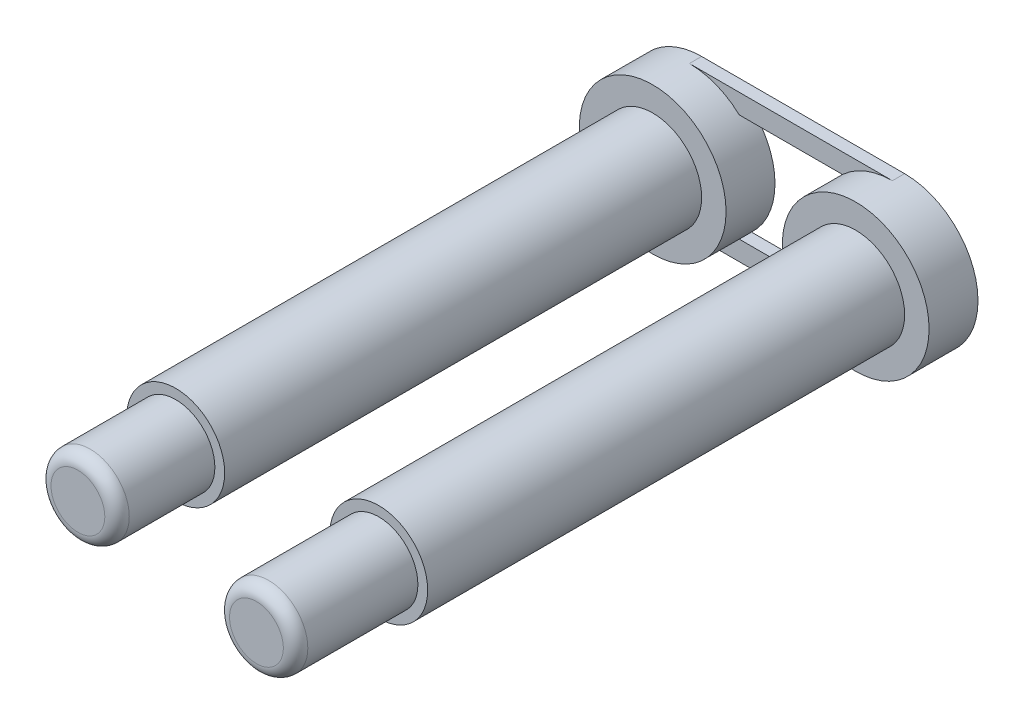
SolidWorks part; units mm, degrees
ref_plane "前视基准面" through (0, 0, 0) normal (0, 0, 1) x (1, 0, 0)
ref_plane "上视基准面" through (0, 0, 0) normal (0, 1, 0) x (1, 0, 0)
ref_plane "右视基准面" through (0, 0, 0) normal (1, 0, 0) x (0, 0, -1)
sketch "Model" plane through (0, 0, 0) normal (0, 0, 1) x (1, 0, 0)
  line L0 (0, 2.26) -> (0, 39.4058)
  line L1 (2.4326, 41.5) -> (50.1564, 41.5)
  line L2 (52.5, 39.422) -> (52.5, 2.28)
  line L3 (50.22, 0) -> (2.26, 0)
  line L4 (0.57, 8.85) -> (-6.93, 8.85)
  line L5 (-6.93, 8.85) -> (-6.93, 24.85)
  line L6 (-6.93, 24.85) -> (0.57, 24.85)
  line L7 (16.57, 8.85) -> (17.57, 8.85)
  line L8 (17.57, 8.85) -> (17.57, 10.85)
  line L9 (17.57, 22.85) -> (17.57, 24.85)
  line L10 (17.57, 24.85) -> (16.57, 24.85)
  line L11 (24.196, 8.775) -> (23.307, 8.775)
  line L12 (22.926, 9.156) -> (22.926, 9.664)
  line L13 (23.307, 10.045) -> (24.196, 10.045)
  line L14 (24.704, 10.045) -> (25.593, 10.045)
  line L15 (25.974, 9.664) -> (25.974, 9.156)
  line L16 (25.593, 8.775) -> (24.704, 8.775)
  line L17 (34.756, 17.315) -> (33.867, 17.315)
  line L18 (33.486, 17.696) -> (33.486, 18.204)
  line L19 (33.867, 18.585) -> (34.756, 18.585)
  line L20 (35.264, 18.585) -> (36.153, 18.585)
  line L21 (36.534, 18.204) -> (36.534, 17.696)
  line L22 (36.153, 17.315) -> (35.264, 17.315)
  line L23 (16.835, 4.806) -> (16.835, 3.917)
  line L24 (16.454, 3.536) -> (15.946, 3.536)
  line L25 (15.565, 3.917) -> (15.565, 4.806)
  line L26 (15.565, 5.314) -> (15.565, 6.203)
  line L27 (15.946, 6.584) -> (16.454, 6.584)
  line L28 (16.835, 6.203) -> (16.835, 5.314)
  line L29 (26.454, 3.425) -> (27.343, 3.425)
  line L30 (27.724, 3.044) -> (27.724, 2.536)
  line L31 (27.343, 2.155) -> (26.454, 2.155)
  line L32 (25.946, 2.155) -> (25.057, 2.155)
  line L33 (24.676, 2.536) -> (24.676, 3.044)
  line L34 (25.057, 3.425) -> (25.946, 3.425)
  line L35 (18.255, 4.756) -> (18.255, 3.867)
  line L36 (17.874, 3.486) -> (17.366, 3.486)
  line L37 (16.985, 3.867) -> (16.985, 4.756)
  line L38 (16.985, 5.264) -> (16.985, 6.153)
  line L39 (17.366, 6.534) -> (17.874, 6.534)
  line L40 (18.255, 6.153) -> (18.255, 5.264)
  line L41 (12.8, 35.75) -> (12.8, 38.8)
  line L42 (12.8, 38.8) -> (14.05, 39.95)
  line L43 (14.05, 39.95) -> (16.45, 39.95)
  line L44 (16.45, 39.95) -> (17.6, 38.9)
  line L45 (17.6, 38.9) -> (17.6, 35.7)
  line L46 (17.6, 35.7) -> (16.45, 34.65)
  line L47 (16.45, 34.65) -> (14, 34.65)
  line L48 (14, 34.65) -> (12.8, 35.75)
  line L49 (3.87, 5.53) -> (6.67, 5.53)
  line L50 (6.67, 5.53) -> (6.67, 4.13)
  line L51 (6.67, 4.13) -> (3.87, 4.13)
  line L52 (3.87, 4.13) -> (3.87, 5.53)
  line L53 (20.8, 6.56) -> (20.8, 9.36)
  line L54 (20.8, 9.36) -> (22.2, 9.36)
  line L55 (22.2, 9.36) -> (22.2, 6.56)
  line L56 (22.2, 6.56) -> (20.8, 6.56)
  line L57 (8.21, 6.97) -> (8.21, 4.17)
  line L58 (8.21, 4.17) -> (6.81, 4.17)
  line L59 (6.81, 4.17) -> (6.81, 6.97)
  line L60 (6.81, 6.97) -> (8.21, 6.97)
  line L61 (10.82, 29.94) -> (10.82, 27.14)
  line L62 (10.82, 27.14) -> (9.42, 27.14)
  line L63 (9.42, 27.14) -> (9.42, 29.94)
  line L64 (9.42, 29.94) -> (10.82, 29.94)
  line L65 (33.69, 12.87) -> (30.89, 12.87)
  line L66 (30.89, 12.87) -> (30.89, 14.27)
  line L67 (30.89, 14.27) -> (33.69, 14.27)
  line L68 (33.69, 14.27) -> (33.69, 12.87)
  line L69 (14.93, 29.94) -> (14.93, 27.14)
  line L70 (14.93, 27.14) -> (13.53, 27.14)
  line L71 (13.53, 27.14) -> (13.53, 29.94)
  line L72 (13.53, 29.94) -> (14.93, 29.94)
  line L73 (26.13, 4.53) -> (26.37, 4.53)
  line L74 (26.37, 4.53) -> (26.37, 7.36)
  line L75 (26.37, 7.36) -> (26.13, 7.36)
  line L76 (22.89, 4.53) -> (22.6, 4.53)
  line L77 (22.6, 4.53) -> (22.6, 7.37)
  line L78 (22.6, 7.37) -> (22.87, 7.37)
  line L79 (1.79, 29.79) -> (6.87, 29.79)
  line L80 (6.87, 29.79) -> (6.87, 27.25)
  line L81 (6.87, 27.25) -> (1.79, 27.25)
  line L82 (1.79, 27.25) -> (1.79, 29.79)
  line L83 (29.996, 38.955) -> (29.107, 38.955)
  line L84 (28.726, 39.336) -> (28.726, 39.844)
  line L85 (29.107, 40.225) -> (29.996, 40.225)
  line L86 (30.504, 40.225) -> (31.393, 40.225)
  line L87 (31.774, 39.844) -> (31.774, 39.336)
  line L88 (31.393, 38.955) -> (30.504, 38.955)
  line L89 (35.825, 11.706) -> (35.825, 10.817)
  line L90 (35.444, 10.436) -> (34.936, 10.436)
  line L91 (34.555, 10.817) -> (34.555, 11.706)
  line L92 (34.555, 12.214) -> (34.555, 13.103)
  line L93 (34.936, 13.484) -> (35.444, 13.484)
  line L94 (35.825, 13.103) -> (35.825, 12.214)
  line L95 (31.416, 6.905) -> (30.527, 6.905)
  line L96 (30.146, 7.286) -> (30.146, 7.794)
  line L97 (30.527, 8.175) -> (31.416, 8.175)
  line L98 (31.924, 8.175) -> (32.813, 8.175)
  line L99 (33.194, 7.794) -> (33.194, 7.286)
  line L100 (32.813, 6.905) -> (31.924, 6.905)
  line L101 (27.125, 13.384) -> (27.125, 14.273)
  line L102 (27.506, 14.654) -> (28.014, 14.654)
  line L103 (28.395, 14.273) -> (28.395, 13.384)
  line L104 (28.395, 12.876) -> (28.395, 11.987)
  line L105 (28.014, 11.606) -> (27.506, 11.606)
  line L106 (27.125, 11.987) -> (27.125, 12.876)
  line L107 (2.726, 5.765) -> (1.837, 5.765)
  line L108 (1.456, 6.146) -> (1.456, 6.654)
  line L109 (1.837, 7.035) -> (2.726, 7.035)
  line L110 (3.234, 7.035) -> (4.123, 7.035)
  line L111 (4.504, 6.654) -> (4.504, 6.146)
  line L112 (4.123, 5.765) -> (3.234, 5.765)
  line L113 (38.274, 36.345) -> (39.163, 36.345)
  line L114 (39.544, 35.964) -> (39.544, 35.456)
  line L115 (39.163, 35.075) -> (38.274, 35.075)
  line L116 (37.766, 35.075) -> (36.877, 35.075)
  line L117 (36.496, 35.456) -> (36.496, 35.964)
  line L118 (36.877, 36.345) -> (37.766, 36.345)
  line L119 (35.295, 38.504) -> (35.295, 39.393)
  line L120 (35.676, 39.774) -> (36.184, 39.774)
  line L121 (36.565, 39.393) -> (36.565, 38.504)
  line L122 (36.565, 37.996) -> (36.565, 37.107)
  line L123 (36.184, 36.726) -> (35.676, 36.726)
  line L124 (35.295, 37.107) -> (35.295, 37.996)
  line L125 (31.265, 4.376) -> (31.265, 3.487)
  line L126 (30.884, 3.106) -> (30.376, 3.106)
  line L127 (29.995, 3.487) -> (29.995, 4.376)
  line L128 (29.995, 4.884) -> (29.995, 5.773)
  line L129 (30.376, 6.154) -> (30.884, 6.154)
  line L130 (31.265, 5.773) -> (31.265, 4.884)
  line L131 (33.42, 4.7325) -> (33.42, 6.15)
  line L132 (33.42, 6.15) -> (31.5, 6.15)
  line L133 (31.5, 6.15) -> (31.5, 4.7325)
  line L134 (33.42, 2.8275) -> (33.42, 1.43)
  line L135 (33.42, 1.43) -> (31.5, 1.43)
  line L136 (31.5, 1.43) -> (31.5, 2.8275)
  line L137 (37.99, 12.2925) -> (37.99, 13.71)
  line L138 (37.99, 13.71) -> (36.07, 13.71)
  line L139 (36.07, 13.71) -> (36.07, 12.2925)
  line L140 (37.99, 10.3875) -> (37.99, 8.99)
  line L141 (37.99, 8.99) -> (36.07, 8.99)
  line L142 (36.07, 8.99) -> (36.07, 10.3875)
  line L143 (37.074, 38.3336) -> (37.074, 37.343)
  line L144 (37.582, 36.835) -> (38.6488, 36.835)
  line L145 (39.106, 37.3176) -> (39.106, 38.3336)
  line L146 (37.074, 39.1464) -> (37.074, 40.137)
  line L147 (37.582, 40.645) -> (38.6488, 40.645)
  line L148 (39.106, 40.1624) -> (39.106, 39.1464)
  line L149 (33.975, 16.983) -> (31.689, 16.983)
  line L150 (31.689, 16.983) -> (31.689, 14.697)
  line L151 (31.689, 14.697) -> (33.975, 14.697)
  line L152 (35.245, 16.983) -> (37.15, 16.983)
  line L153 (37.15, 16.983) -> (37.531, 16.602)
  line L154 (37.531, 16.602) -> (37.531, 15.078)
  line L155 (37.531, 15.078) -> (37.15, 14.697)
  line L156 (37.15, 14.697) -> (35.245, 14.697)
  line L157 (21.1, 35.75) -> (21.1, 38.8)
  line L158 (21.1, 38.8) -> (22.35, 39.95)
  line L159 (22.35, 39.95) -> (24.75, 39.95)
  line L160 (24.75, 39.95) -> (25.9, 38.9)
  line L161 (25.9, 38.9) -> (25.9, 35.7)
  line L162 (25.9, 35.7) -> (24.75, 34.65)
  line L163 (24.75, 34.65) -> (22.3, 34.65)
  line L164 (22.3, 34.65) -> (21.1, 35.75)
  line L165 (5.44, 35.75) -> (5.44, 38.8)
  line L166 (5.44, 38.8) -> (6.69, 39.95)
  line L167 (6.69, 39.95) -> (9.09, 39.95)
  line L168 (9.09, 39.95) -> (10.24, 38.9)
  line L169 (10.24, 38.9) -> (10.24, 35.7)
  line L170 (10.24, 35.7) -> (9.09, 34.65)
  line L171 (9.09, 34.65) -> (6.64, 34.65)
  line L172 (6.64, 34.65) -> (5.44, 35.75)
  line L173 (34.57, 3.22) -> (38.57, 3.22)
  line L174 (38.57, 3.22) -> (38.57, 8.72)
  line L175 (38.57, 8.72) -> (34.57, 8.72)
  line L176 (34.57, 8.72) -> (34.57, 3.22)
  line L177 (39.81, 30.07) -> (37.01, 30.07)
  line L178 (37.01, 30.07) -> (37.01, 31.47)
  line L179 (37.01, 31.47) -> (39.81, 31.47)
  line L180 (39.81, 31.47) -> (39.81, 30.07)
  line L181 (28.51, 40.17) -> (28.51, 37.37)
  line L182 (28.51, 37.37) -> (27.11, 37.37)
  line L183 (27.11, 37.37) -> (27.11, 40.17)
  line L184 (27.11, 40.17) -> (28.51, 40.17)
  line L185 (32.06, 40.25) -> (34.86, 40.25)
  line L186 (34.86, 40.25) -> (34.86, 38.85)
  line L187 (34.86, 38.85) -> (32.06, 38.85)
  line L188 (32.06, 38.85) -> (32.06, 40.25)
  line L189 (28.56, 11.71) -> (28.56, 14.51)
  line L190 (28.56, 14.51) -> (29.96, 14.51)
  line L191 (29.96, 14.51) -> (29.96, 11.71)
  line L192 (29.96, 11.71) -> (28.56, 11.71)
  line L193 (25.54, 13.29) -> (25.54, 16.09)
  line L194 (25.54, 16.09) -> (26.94, 16.09)
  line L195 (26.94, 16.09) -> (26.94, 13.29)
  line L196 (26.94, 13.29) -> (25.54, 13.29)
  line L197 (27.11, 11.4) -> (29.91, 11.4)
  line L198 (29.91, 11.4) -> (29.91, 10)
  line L199 (29.91, 10) -> (27.11, 10)
  line L200 (27.11, 10) -> (27.11, 11.4)
  line L201 (29.06, 8.4) -> (26.26, 8.4)
  line L202 (26.26, 8.4) -> (26.26, 9.8)
  line L203 (26.26, 9.8) -> (29.06, 9.8)
  line L204 (29.06, 9.8) -> (29.06, 8.4)
  line L205 (18.53, 32.56) -> (18.53, 29.76)
  line L206 (18.53, 29.76) -> (17.13, 29.76)
  line L207 (17.13, 29.76) -> (17.13, 32.56)
  line L208 (17.13, 32.56) -> (18.53, 32.56)
  line L209 (5.02, 31.95) -> (2.22, 31.95)
  line L210 (2.22, 31.95) -> (2.22, 33.35)
  line L211 (2.22, 33.35) -> (5.02, 33.35)
  line L212 (5.02, 33.35) -> (5.02, 31.95)
  line L213 (9.22, 29.96) -> (9.22, 27.16)
  line L214 (9.22, 27.16) -> (7.82, 27.16)
  line L215 (7.82, 27.16) -> (7.82, 29.96)
  line L216 (7.82, 29.96) -> (9.22, 29.96)
  line L217 (25.54, 18.87) -> (28.34, 18.87)
  line L218 (28.34, 18.87) -> (28.34, 17.47)
  line L219 (28.34, 17.47) -> (25.54, 17.47)
  line L220 (25.54, 17.47) -> (25.54, 18.87)
  line L221 (28.31, 19.13) -> (25.51, 19.13)
  line L222 (25.51, 19.13) -> (25.51, 20.53)
  line L223 (25.51, 20.53) -> (28.31, 20.53)
  line L224 (28.31, 20.53) -> (28.31, 19.13)
  line L225 (8.87, 4.41) -> (8.87, 7.21)
  line L226 (8.87, 7.21) -> (10.27, 7.21)
  line L227 (10.27, 7.21) -> (10.27, 4.41)
  line L228 (10.27, 4.41) -> (8.87, 4.41)
  line L229 (11.05, 4.16) -> (11.05, 6.96)
  line L230 (11.05, 6.96) -> (12.45, 6.96)
  line L231 (12.45, 6.96) -> (12.45, 4.16)
  line L232 (12.45, 4.16) -> (11.05, 4.16)
  line L233 (7.61, 30.34) -> (4.81, 30.34)
  line L234 (4.81, 30.34) -> (4.81, 31.74)
  line L235 (4.81, 31.74) -> (7.61, 31.74)
  line L236 (7.61, 31.74) -> (7.61, 30.34)
  line L237 (4.24, 30.32) -> (1.44, 30.32)
  line L238 (1.44, 30.32) -> (1.44, 31.72)
  line L239 (1.44, 31.72) -> (4.24, 31.72)
  line L240 (4.24, 31.72) -> (4.24, 30.32)
  line L241 (39.81, 31.61) -> (37.01, 31.61)
  line L242 (37.01, 31.61) -> (37.01, 33.01)
  line L243 (37.01, 33.01) -> (39.81, 33.01)
  line L244 (39.81, 33.01) -> (39.81, 31.61)
  line L245 (30.83, 8.94) -> (30.83, 8.7)
  line L246 (30.83, 8.7) -> (33.66, 8.7)
  line L247 (33.66, 8.7) -> (33.66, 8.94)
  line L248 (30.83, 12.18) -> (30.83, 12.47)
  line L249 (30.83, 12.47) -> (33.67, 12.47)
  line L250 (33.67, 12.47) -> (33.67, 12.2)
  line L251 (51.33, 22.79) -> (51.33, 33.29)
  line L252 (51.33, 33.29) -> (45.93, 33.29)
  line L253 (45.93, 33.29) -> (45.93, 22.79)
  line L254 (45.93, 22.79) -> (46.63, 22.09)
  line L255 (46.63, 22.09) -> (50.63, 22.09)
  line L256 (50.63, 22.09) -> (51.33, 22.79)
  line L257 (48.63, 35.31) -> (48.63, 33.278)
  line L258 (49.646, 34.294) -> (47.614, 34.294)
  line L259 (51.38, 7.21) -> (51.38, 17.71)
  line L260 (51.38, 17.71) -> (45.98, 17.71)
  line L261 (45.98, 17.71) -> (45.98, 7.21)
  line L262 (45.98, 7.21) -> (46.68, 6.51)
  line L263 (46.68, 6.51) -> (50.68, 6.51)
  line L264 (50.68, 6.51) -> (51.38, 7.21)
  line L265 (48.68, 19.73) -> (48.68, 17.698)
  line L266 (49.696, 18.714) -> (47.664, 18.714)
  line L267 (31.402, 24.62) -> (31.402, 19.54)
  line L268 (31.402, 19.54) -> (34.958, 19.54)
  line L269 (34.958, 19.54) -> (34.958, 24.62)
  line L270 (34.958, 24.62) -> (31.402, 24.62)
  line L271 (33.942, 24.62) -> (33.942, 24.112)
  line L272 (33.942, 24.112) -> (32.418, 24.112)
  line L273 (32.418, 24.112) -> (32.418, 24.62)
  line L274 (35.323, 25.5545) -> (37.482, 25.5545)
  line L275 (37.482, 25.5545) -> (37.482, 29.7455)
  line L276 (37.482, 29.7455) -> (35.323, 29.7455)
  line L277 (30.497, 25.5545) -> (28.338, 25.5545)
  line L278 (28.338, 25.5545) -> (28.338, 29.7455)
  line L279 (28.338, 29.7455) -> (30.497, 29.7455)
  line L280 (39.675, 36.4523) -> (39.675, 38.9337)
  line L281 (39.675, 38.9337) -> (39.6757, 38.9337)
  line L282 (39.6757, 38.9337) -> (39.6757, 41.34)
  line L283 (39.6757, 41.34) -> (47.0987, 41.34)
  line L284 (47.0987, 41.34) -> (47.0987, 36.4523)
  line L285 (47.0987, 36.4523) -> (39.675, 36.4523)
  line L286 (39.674, 41.32) -> (47.0987, 41.32)
  line L287 (47.0987, 41.32) -> (47.0987, 41.84)
  line L288 (47.0987, 41.84) -> (39.674, 41.84)
  line L289 (39.674, 41.84) -> (39.674, 41.32)
  line L290 (40.55, 41.34) -> (40.12, 41.77)
  line L291 (46.28, 41.37) -> (46.71, 41.8)
  line L292 (35.28, 32.52) -> (35.28, 31.92)
  line L293 (35.28, 31.92) -> (34.88, 31.52)
  line L294 (34.88, 31.52) -> (34.38, 31.52)
  line L295 (34.98, 36.32) -> (34.98, 36.82)
  line L296 (34.98, 36.82) -> (34.48, 36.82)
  line L297 (29.98, 36.32) -> (29.98, 36.82)
  line L298 (29.98, 36.82) -> (30.48, 36.82)
  line L299 (29.98, 32.32) -> (29.98, 31.82)
  line L300 (29.98, 31.82) -> (30.48, 31.82)
  arc A0 (0, 2.26) -> (2.26, 0) centre (2.5947, 2.5947) ccw
  arc A1 (2.4326, 41.5) -> (0, 39.4058) centre (2.365, 39.1186) ccw
  arc A2 (52.5, 39.422) -> (50.1564, 41.5) centre (50.2928, 39.2933) ccw
  arc A3 (50.22, 0) -> (52.5, 2.28) centre (50.2397, 2.2603) ccw
  circle A4 centre (2.26, 0) radius 0.0635
  circle A5 centre (0, 2.26) radius 0.0635
  circle A6 centre (0, 39.4058) radius 0.0635
  circle A7 centre (2.4326, 41.5) radius 0.0635
  circle A8 centre (50.1564, 41.5) radius 0.0635
  circle A9 centre (52.5, 39.422) radius 0.0635
  circle A10 centre (52.5, 2.28) radius 0.0635
  circle A11 centre (2, 39.5) radius 1.1
  circle A12 centre (50.5, 39.5) radius 1.1
  circle A13 centre (50.5, 2) radius 1.1
  circle A14 centre (2, 2) radius 1.1
  circle A15 centre (0.57, 8.85) radius 0.0635
  circle A16 centre (-6.93, 8.85) radius 0.0635
  circle A17 centre (-6.93, 24.85) radius 0.0635
  circle A18 centre (0.57, 24.85) radius 0.0635
  circle A19 centre (16.57, 8.85) radius 0.0635
  circle A20 centre (17.57, 8.85) radius 0.0635
  circle A21 centre (17.57, 10.85) radius 0.0635
  circle A22 centre (17.57, 22.85) radius 0.0635
  circle A23 centre (17.57, 24.85) radius 0.0635
  circle A24 centre (16.57, 24.85) radius 0.0635
  circle A25 centre (1.57, 7.55) radius 0.3606
  arc A26 (22.926, 9.156) -> (23.307, 8.775) centre (23.307, 9.156) ccw
  arc A27 (23.307, 10.045) -> (22.926, 9.664) centre (23.307, 9.664) ccw
  circle A28 centre (24.196, 8.775) radius 0.025
  circle A29 centre (23.307, 8.775) radius 0.025
  arc A30 (25.974, 9.664) -> (25.593, 10.045) centre (25.593, 9.664) ccw
  arc A31 (25.593, 8.775) -> (25.974, 9.156) centre (25.593, 9.156) ccw
  circle A32 centre (24.704, 10.045) radius 0.025
  circle A33 centre (25.593, 10.045) radius 0.025
  arc A34 (33.486, 17.696) -> (33.867, 17.315) centre (33.867, 17.696) ccw
  arc A35 (33.867, 18.585) -> (33.486, 18.204) centre (33.867, 18.204) ccw
  circle A36 centre (34.756, 17.315) radius 0.025
  circle A37 centre (33.867, 17.315) radius 0.025
  arc A38 (36.534, 18.204) -> (36.153, 18.585) centre (36.153, 18.204) ccw
  arc A39 (36.153, 17.315) -> (36.534, 17.696) centre (36.153, 17.696) ccw
  circle A40 centre (35.264, 18.585) radius 0.025
  circle A41 centre (36.153, 18.585) radius 0.025
  arc A42 (16.454, 3.536) -> (16.835, 3.917) centre (16.454, 3.917) ccw
  arc A43 (15.565, 3.917) -> (15.946, 3.536) centre (15.946, 3.917) ccw
  circle A44 centre (16.835, 4.806) radius 0.025
  circle A45 centre (16.835, 3.917) radius 0.025
  arc A46 (15.946, 6.584) -> (15.565, 6.203) centre (15.946, 6.203) ccw
  arc A47 (16.835, 6.203) -> (16.454, 6.584) centre (16.454, 6.203) ccw
  circle A48 centre (15.565, 5.314) radius 0.025
  circle A49 centre (15.565, 6.203) radius 0.025
  arc A50 (27.724, 3.044) -> (27.343, 3.425) centre (27.343, 3.044) ccw
  arc A51 (27.343, 2.155) -> (27.724, 2.536) centre (27.343, 2.536) ccw
  circle A52 centre (26.454, 3.425) radius 0.025
  circle A53 centre (27.343, 3.425) radius 0.025
  arc A54 (24.676, 2.536) -> (25.057, 2.155) centre (25.057, 2.536) ccw
  arc A55 (25.057, 3.425) -> (24.676, 3.044) centre (25.057, 3.044) ccw
  circle A56 centre (25.946, 2.155) radius 0.025
  circle A57 centre (25.057, 2.155) radius 0.025
  arc A58 (17.874, 3.486) -> (18.255, 3.867) centre (17.874, 3.867) ccw
  arc A59 (16.985, 3.867) -> (17.366, 3.486) centre (17.366, 3.867) ccw
  circle A60 centre (18.255, 4.756) radius 0.025
  circle A61 centre (18.255, 3.867) radius 0.025
  arc A62 (17.366, 6.534) -> (16.985, 6.153) centre (17.366, 6.153) ccw
  arc A63 (18.255, 6.153) -> (17.874, 6.534) centre (17.874, 6.153) ccw
  circle A64 centre (16.985, 5.264) radius 0.025
  circle A65 centre (16.985, 6.153) radius 0.025
  circle A66 centre (12.8, 35.75) radius 0.0375
  circle A67 centre (12.8, 38.8) radius 0.0375
  circle A68 centre (14.05, 39.95) radius 0.0375
  circle A69 centre (16.45, 39.95) radius 0.0375
  circle A70 centre (17.6, 38.9) radius 0.0375
  circle A71 centre (17.6, 35.7) radius 0.0375
  circle A72 centre (16.45, 34.65) radius 0.0375
  circle A73 centre (14, 34.65) radius 0.0375
  circle A74 centre (15.2, 37.3) radius 1.5
  circle A75 centre (15.2, 37.3) radius 0.7566
  circle A76 centre (3.87, 5.53) radius 0.0375
  circle A77 centre (6.67, 5.53) radius 0.0375
  circle A78 centre (6.67, 4.13) radius 0.0375
  circle A79 centre (3.87, 4.13) radius 0.0375
  circle A80 centre (20.8, 6.56) radius 0.0375
  circle A81 centre (20.8, 9.36) radius 0.0375
  circle A82 centre (22.2, 9.36) radius 0.0375
  circle A83 centre (22.2, 6.56) radius 0.0375
  circle A84 centre (8.21, 6.97) radius 0.0375
  circle A85 centre (8.21, 4.17) radius 0.0375
  circle A86 centre (6.81, 4.17) radius 0.0375
  circle A87 centre (6.81, 6.97) radius 0.0375
  circle A88 centre (10.82, 29.94) radius 0.0375
  circle A89 centre (10.82, 27.14) radius 0.0375
  circle A90 centre (9.42, 27.14) radius 0.0375
  circle A91 centre (9.42, 29.94) radius 0.0375
  circle A92 centre (33.69, 12.87) radius 0.0375
  circle A93 centre (30.89, 12.87) radius 0.0375
  circle A94 centre (30.89, 14.27) radius 0.0375
  circle A95 centre (33.69, 14.27) radius 0.0375
  circle A96 centre (14.93, 29.94) radius 0.0375
  circle A97 centre (14.93, 27.14) radius 0.0375
  circle A98 centre (13.53, 27.14) radius 0.0375
  circle A99 centre (13.53, 29.94) radius 0.0375
  circle A100 centre (26.13, 4.53) radius 0.05
  circle A101 centre (26.37, 4.53) radius 0.05
  circle A102 centre (26.37, 7.36) radius 0.05
  circle A103 centre (26.13, 7.36) radius 0.05
  circle A104 centre (22.89, 4.53) radius 0.05
  circle A105 centre (22.6, 4.53) radius 0.05
  circle A106 centre (22.6, 7.37) radius 0.05
  circle A107 centre (22.87, 7.37) radius 0.05
  circle A108 centre (1.79, 29.79) radius 0.0635
  circle A109 centre (6.87, 29.79) radius 0.0635
  circle A110 centre (6.87, 27.25) radius 0.0635
  circle A111 centre (1.79, 27.25) radius 0.0635
  arc A112 (28.726, 39.336) -> (29.107, 38.955) centre (29.107, 39.336) ccw
  arc A113 (29.107, 40.225) -> (28.726, 39.844) centre (29.107, 39.844) ccw
  circle A114 centre (29.996, 38.955) radius 0.025
  circle A115 centre (29.107, 38.955) radius 0.025
  arc A116 (31.774, 39.844) -> (31.393, 40.225) centre (31.393, 39.844) ccw
  arc A117 (31.393, 38.955) -> (31.774, 39.336) centre (31.393, 39.336) ccw
  circle A118 centre (30.504, 40.225) radius 0.025
  circle A119 centre (31.393, 40.225) radius 0.025
  arc A120 (35.444, 10.436) -> (35.825, 10.817) centre (35.444, 10.817) ccw
  arc A121 (34.555, 10.817) -> (34.936, 10.436) centre (34.936, 10.817) ccw
  circle A122 centre (35.825, 11.706) radius 0.025
  circle A123 centre (35.825, 10.817) radius 0.025
  arc A124 (34.936, 13.484) -> (34.555, 13.103) centre (34.936, 13.103) ccw
  arc A125 (35.825, 13.103) -> (35.444, 13.484) centre (35.444, 13.103) ccw
  circle A126 centre (34.555, 12.214) radius 0.025
  circle A127 centre (34.555, 13.103) radius 0.025
  arc A128 (30.146, 7.286) -> (30.527, 6.905) centre (30.527, 7.286) ccw
  arc A129 (30.527, 8.175) -> (30.146, 7.794) centre (30.527, 7.794) ccw
  circle A130 centre (31.416, 6.905) radius 0.025
  circle A131 centre (30.527, 6.905) radius 0.025
  arc A132 (33.194, 7.794) -> (32.813, 8.175) centre (32.813, 7.794) ccw
  arc A133 (32.813, 6.905) -> (33.194, 7.286) centre (32.813, 7.286) ccw
  circle A134 centre (31.924, 8.175) radius 0.025
  circle A135 centre (32.813, 8.175) radius 0.025
  arc A136 (27.506, 14.654) -> (27.125, 14.273) centre (27.506, 14.273) ccw
  arc A137 (28.395, 14.273) -> (28.014, 14.654) centre (28.014, 14.273) ccw
  circle A138 centre (27.125, 13.384) radius 0.025
  circle A139 centre (27.125, 14.273) radius 0.025
  arc A140 (28.014, 11.606) -> (28.395, 11.987) centre (28.014, 11.987) ccw
  arc A141 (27.125, 11.987) -> (27.506, 11.606) centre (27.506, 11.987) ccw
  circle A142 centre (28.395, 12.876) radius 0.025
  circle A143 centre (28.395, 11.987) radius 0.025
  arc A144 (1.456, 6.146) -> (1.837, 5.765) centre (1.837, 6.146) ccw
  arc A145 (1.837, 7.035) -> (1.456, 6.654) centre (1.837, 6.654) ccw
  circle A146 centre (2.726, 5.765) radius 0.025
  circle A147 centre (1.837, 5.765) radius 0.025
  arc A148 (4.504, 6.654) -> (4.123, 7.035) centre (4.123, 6.654) ccw
  arc A149 (4.123, 5.765) -> (4.504, 6.146) centre (4.123, 6.146) ccw
  circle A150 centre (3.234, 7.035) radius 0.025
  circle A151 centre (4.123, 7.035) radius 0.025
  arc A152 (39.544, 35.964) -> (39.163, 36.345) centre (39.163, 35.964) ccw
  arc A153 (39.163, 35.075) -> (39.544, 35.456) centre (39.163, 35.456) ccw
  circle A154 centre (38.274, 36.345) radius 0.025
  circle A155 centre (39.163, 36.345) radius 0.025
  arc A156 (36.496, 35.456) -> (36.877, 35.075) centre (36.877, 35.456) ccw
  arc A157 (36.877, 36.345) -> (36.496, 35.964) centre (36.877, 35.964) ccw
  circle A158 centre (37.766, 35.075) radius 0.025
  circle A159 centre (36.877, 35.075) radius 0.025
  arc A160 (35.676, 39.774) -> (35.295, 39.393) centre (35.676, 39.393) ccw
  arc A161 (36.565, 39.393) -> (36.184, 39.774) centre (36.184, 39.393) ccw
  circle A162 centre (35.295, 38.504) radius 0.025
  circle A163 centre (35.295, 39.393) radius 0.025
  arc A164 (36.184, 36.726) -> (36.565, 37.107) centre (36.184, 37.107) ccw
  arc A165 (35.295, 37.107) -> (35.676, 36.726) centre (35.676, 37.107) ccw
  circle A166 centre (36.565, 37.996) radius 0.025
  circle A167 centre (36.565, 37.107) radius 0.025
  arc A168 (30.884, 3.106) -> (31.265, 3.487) centre (30.884, 3.487) ccw
  arc A169 (29.995, 3.487) -> (30.376, 3.106) centre (30.376, 3.487) ccw
  circle A170 centre (31.265, 4.376) radius 0.025
  circle A171 centre (31.265, 3.487) radius 0.025
  arc A172 (30.376, 6.154) -> (29.995, 5.773) centre (30.376, 5.773) ccw
  arc A173 (31.265, 5.773) -> (30.884, 6.154) centre (30.884, 5.773) ccw
  circle A174 centre (29.995, 4.884) radius 0.025
  circle A175 centre (29.995, 5.773) radius 0.025
  circle A176 centre (33.42, 4.7325) radius 0.0635
  circle A177 centre (33.42, 6.15) radius 0.0635
  circle A178 centre (31.5, 6.15) radius 0.0635
  circle A179 centre (31.5, 4.7325) radius 0.0635
  circle A180 centre (33.42, 2.8275) radius 0.0635
  circle A181 centre (33.42, 1.43) radius 0.0635
  circle A182 centre (31.5, 1.43) radius 0.0635
  circle A183 centre (31.5, 2.8275) radius 0.0635
  circle A184 centre (37.99, 12.2925) radius 0.0635
  circle A185 centre (37.99, 13.71) radius 0.0635
  circle A186 centre (36.07, 13.71) radius 0.0635
  circle A187 centre (36.07, 12.2925) radius 0.0635
  circle A188 centre (37.99, 10.3875) radius 0.0635
  circle A189 centre (37.99, 8.99) radius 0.0635
  circle A190 centre (36.07, 8.99) radius 0.0635
  circle A191 centre (36.07, 10.3875) radius 0.0635
  arc A192 (37.074, 37.343) -> (37.582, 36.835) centre (37.582, 37.343) ccw
  arc A193 (38.6488, 36.835) -> (39.106, 37.3176) centre (38.6361, 37.3049) ccw
  circle A194 centre (37.074, 38.3336) radius 0.0254
  circle A195 centre (37.074, 37.343) radius 0.0254
  arc A196 (37.582, 40.645) -> (37.074, 40.137) centre (37.582, 40.137) ccw
  arc A197 (39.106, 40.1624) -> (38.6488, 40.645) centre (38.6361, 40.1751) ccw
  circle A198 centre (37.074, 39.1464) radius 0.0254
  circle A199 centre (37.074, 40.137) radius 0.0254
  circle A200 centre (33.975, 16.983) radius 0.0635
  circle A201 centre (31.689, 16.983) radius 0.0635
  circle A202 centre (31.689, 14.697) radius 0.0635
  circle A203 centre (33.975, 14.697) radius 0.0635
  circle A204 centre (35.245, 16.983) radius 0.0635
  circle A205 centre (37.15, 16.983) radius 0.0635
  circle A206 centre (37.531, 16.602) radius 0.0635
  circle A207 centre (37.531, 15.078) radius 0.0635
  circle A208 centre (37.15, 14.697) radius 0.0635
  circle A209 centre (35.245, 14.697) radius 0.0635
  circle A210 centre (21.1, 35.75) radius 0.0375
  circle A211 centre (21.1, 38.8) radius 0.0375
  circle A212 centre (22.35, 39.95) radius 0.0375
  circle A213 centre (24.75, 39.95) radius 0.0375
  circle A214 centre (25.9, 38.9) radius 0.0375
  circle A215 centre (25.9, 35.7) radius 0.0375
  circle A216 centre (24.75, 34.65) radius 0.0375
  circle A217 centre (22.3, 34.65) radius 0.0375
  circle A218 centre (23.5, 37.3) radius 1.5
  circle A219 centre (23.5, 37.3) radius 0.7566
  circle A220 centre (5.44, 35.75) radius 0.0375
  circle A221 centre (5.44, 38.8) radius 0.0375
  circle A222 centre (6.69, 39.95) radius 0.0375
  circle A223 centre (9.09, 39.95) radius 0.0375
  circle A224 centre (10.24, 38.9) radius 0.0375
  circle A225 centre (10.24, 35.7) radius 0.0375
  circle A226 centre (9.09, 34.65) radius 0.0375
  circle A227 centre (6.64, 34.65) radius 0.0375
  circle A228 centre (7.84, 37.3) radius 1.5
  circle A229 centre (7.84, 37.3) radius 0.7566
  circle A230 centre (34.57, 3.22) radius 0.0381
  circle A231 centre (38.57, 3.22) radius 0.0381
  circle A232 centre (38.57, 8.72) radius 0.0381
  circle A233 centre (34.57, 8.72) radius 0.0381
  circle A234 centre (39.81, 30.07) radius 0.0375
  circle A235 centre (37.01, 30.07) radius 0.0375
  circle A236 centre (37.01, 31.47) radius 0.0375
  circle A237 centre (39.81, 31.47) radius 0.0375
  circle A238 centre (28.51, 40.17) radius 0.0375
  circle A239 centre (28.51, 37.37) radius 0.0375
  circle A240 centre (27.11, 37.37) radius 0.0375
  circle A241 centre (27.11, 40.17) radius 0.0375
  circle A242 centre (32.06, 40.25) radius 0.0375
  circle A243 centre (34.86, 40.25) radius 0.0375
  circle A244 centre (34.86, 38.85) radius 0.0375
  circle A245 centre (32.06, 38.85) radius 0.0375
  circle A246 centre (28.56, 11.71) radius 0.0375
  circle A247 centre (28.56, 14.51) radius 0.0375
  circle A248 centre (29.96, 14.51) radius 0.0375
  circle A249 centre (29.96, 11.71) radius 0.0375
  circle A250 centre (25.54, 13.29) radius 0.0375
  circle A251 centre (25.54, 16.09) radius 0.0375
  circle A252 centre (26.94, 16.09) radius 0.0375
  circle A253 centre (26.94, 13.29) radius 0.0375
  circle A254 centre (27.11, 11.4) radius 0.0375
  circle A255 centre (29.91, 11.4) radius 0.0375
  circle A256 centre (29.91, 10) radius 0.0375
  circle A257 centre (27.11, 10) radius 0.0375
  circle A258 centre (29.06, 8.4) radius 0.0375
  circle A259 centre (26.26, 8.4) radius 0.0375
  circle A260 centre (26.26, 9.8) radius 0.0375
  circle A261 centre (29.06, 9.8) radius 0.0375
  circle A262 centre (18.53, 32.56) radius 0.0375
  circle A263 centre (18.53, 29.76) radius 0.0375
  circle A264 centre (17.13, 29.76) radius 0.0375
  circle A265 centre (17.13, 32.56) radius 0.0375
  circle A266 centre (5.02, 31.95) radius 0.0375
  circle A267 centre (2.22, 31.95) radius 0.0375
  circle A268 centre (2.22, 33.35) radius 0.0375
  circle A269 centre (5.02, 33.35) radius 0.0375
  circle A270 centre (9.22, 29.96) radius 0.0375
  circle A271 centre (9.22, 27.16) radius 0.0375
  circle A272 centre (7.82, 27.16) radius 0.0375
  circle A273 centre (7.82, 29.96) radius 0.0375
  circle A274 centre (25.54, 18.87) radius 0.0375
  circle A275 centre (28.34, 18.87) radius 0.0375
  circle A276 centre (28.34, 17.47) radius 0.0375
  circle A277 centre (25.54, 17.47) radius 0.0375
  circle A278 centre (28.31, 19.13) radius 0.0375
  circle A279 centre (25.51, 19.13) radius 0.0375
  circle A280 centre (25.51, 20.53) radius 0.0375
  circle A281 centre (28.31, 20.53) radius 0.0375
  circle A282 centre (8.87, 4.41) radius 0.0375
  circle A283 centre (8.87, 7.21) radius 0.0375
  circle A284 centre (10.27, 7.21) radius 0.0375
  circle A285 centre (10.27, 4.41) radius 0.0375
  circle A286 centre (11.05, 4.16) radius 0.0375
  circle A287 centre (11.05, 6.96) radius 0.0375
  circle A288 centre (12.45, 6.96) radius 0.0375
  circle A289 centre (12.45, 4.16) radius 0.0375
  circle A290 centre (7.61, 30.34) radius 0.0375
  circle A291 centre (4.81, 30.34) radius 0.0375
  circle A292 centre (4.81, 31.74) radius 0.0375
  circle A293 centre (7.61, 31.74) radius 0.0375
  circle A294 centre (4.24, 30.32) radius 0.0375
  circle A295 centre (1.44, 30.32) radius 0.0375
  circle A296 centre (1.44, 31.72) radius 0.0375
  circle A297 centre (4.24, 31.72) radius 0.0375
  circle A298 centre (39.81, 31.61) radius 0.0375
  circle A299 centre (37.01, 31.61) radius 0.0375
  circle A300 centre (37.01, 33.01) radius 0.0375
  circle A301 centre (39.81, 33.01) radius 0.0375
  circle A302 centre (30.83, 8.94) radius 0.05
  circle A303 centre (30.83, 8.7) radius 0.05
  circle A304 centre (33.66, 8.7) radius 0.05
  circle A305 centre (33.66, 8.94) radius 0.05
  circle A306 centre (30.83, 12.18) radius 0.05
  circle A307 centre (30.83, 12.47) radius 0.05
  circle A308 centre (33.67, 12.47) radius 0.05
  circle A309 centre (33.67, 12.2) radius 0.05
  circle A310 centre (33.43, 8.97) radius 0.2343
  circle A311 centre (51.33, 22.79) radius 0.0635
  circle A312 centre (51.33, 33.29) radius 0.0635
  circle A313 centre (45.93, 33.29) radius 0.0635
  circle A314 centre (45.93, 22.79) radius 0.0635
  circle A315 centre (46.63, 22.09) radius 0.0635
  circle A316 centre (50.63, 22.09) radius 0.0635
  circle A317 centre (48.63, 35.31) radius 0.0635
  circle A318 centre (48.63, 33.278) radius 0.0635
  circle A319 centre (49.646, 34.294) radius 0.0635
  circle A320 centre (47.614, 34.294) radius 0.0635
  circle A321 centre (51.38, 7.21) radius 0.0635
  circle A322 centre (51.38, 17.71) radius 0.0635
  circle A323 centre (45.98, 17.71) radius 0.0635
  circle A324 centre (45.98, 7.21) radius 0.0635
  circle A325 centre (46.68, 6.51) radius 0.0635
  circle A326 centre (50.68, 6.51) radius 0.0635
  circle A327 centre (48.68, 19.73) radius 0.0635
  circle A328 centre (48.68, 17.698) radius 0.0635
  circle A329 centre (49.696, 18.714) radius 0.0635
  circle A330 centre (47.664, 18.714) radius 0.0635
  circle A331 centre (31.402, 24.62) radius 0.0635
  circle A332 centre (31.402, 19.54) radius 0.0635
  circle A333 centre (34.958, 19.54) radius 0.0635
  circle A334 centre (34.958, 24.62) radius 0.0635
  circle A335 centre (30.132, 24.874) radius 0.1778
  circle A336 centre (33.942, 24.62) radius 0.0635
  circle A337 centre (33.942, 24.112) radius 0.0635
  circle A338 centre (32.418, 24.112) radius 0.0635
  circle A339 centre (32.418, 24.62) radius 0.0635
  circle A340 centre (35.323, 25.5545) radius 0.0635
  circle A341 centre (37.482, 25.5545) radius 0.0635
  circle A342 centre (37.482, 29.7455) radius 0.0635
  circle A343 centre (35.323, 29.7455) radius 0.0635
  circle A344 centre (30.497, 25.5545) radius 0.0635
  circle A345 centre (28.338, 25.5545) radius 0.0635
  circle A346 centre (28.338, 29.7455) radius 0.0635
  circle A347 centre (30.497, 29.7455) radius 0.0635
  circle A348 centre (39.675, 36.4523) radius 0.0375
  circle A349 centre (39.675, 38.9337) radius 0.0375
  circle A350 centre (39.6757, 38.9337) radius 0.0375
  circle A351 centre (39.6757, 41.34) radius 0.0375
  circle A352 centre (47.0987, 41.34) radius 0.0375
  circle A353 centre (47.0987, 36.4523) radius 0.0375
  circle A354 centre (39.674, 41.32) radius 0.0375
  circle A355 centre (47.0987, 41.32) radius 0.0375
  circle A356 centre (47.0987, 41.84) radius 0.0375
  circle A357 centre (39.674, 41.84) radius 0.0375
  circle A358 centre (40.55, 41.34) radius 0.0375
  circle A359 centre (40.12, 41.77) radius 0.0375
  circle A360 centre (46.28, 41.37) radius 0.0375
  circle A361 centre (46.71, 41.8) radius 0.0375
  circle A362 centre (35.28, 32.52) radius 0.05
  circle A363 centre (35.28, 31.92) radius 0.05
  circle A364 centre (34.88, 31.52) radius 0.05
  circle A365 centre (34.38, 31.52) radius 0.05
  circle A366 centre (34.98, 36.32) radius 0.05
  circle A367 centre (34.98, 36.82) radius 0.05
  circle A368 centre (34.48, 36.82) radius 0.05
  circle A369 centre (29.98, 36.32) radius 0.05
  circle A370 centre (29.98, 36.82) radius 0.05
  circle A371 centre (30.48, 36.82) radius 0.05
  circle A372 centre (29.98, 32.32) radius 0.05
  circle A373 centre (29.98, 31.82) radius 0.05
  circle A374 centre (30.48, 31.82) radius 0.05
sketch "草图2" plane through (0, 0, 0) normal (0, 0, 1) x (1, 0, 0)
  line L2 (-6.6015, 41.501) -> (53.5, 41.501)
  line L10 (-6.6015, -1) -> (53.5, -1)
  line L11 (53.5, 41.501) -> (53.5, -1)
  line L14 (-9.6015, 41.501) -> (-9.6015, 0) construction
  line L15 (-9.6015, 0) -> (0, 0) construction
  line L16 (0, 0) -> (52.5, 0) construction
  line L17 (52.5, 41.501) -> (52.5, 0) construction
  line L18 (-8.6015, -3) -> (0, -3)
  line L19 (0, -3) -> (55.5, -3)
  line L20 (55.5, 43.001) -> (55.5, -3)
  line L23 (0, 42.501) -> (53.5, 42.501) construction
  line L24 (0, 42.501) -> (-10.6015, 42.501) construction
  line L25 (0, 43.001) -> (55.5, 43.001)
  line L26 (0, 43.001) -> (-8.6015, 43.001)
  line L27 (0, 41.501) -> (-9.6015, 41.501) construction
  line L28 (0, 41.501) -> (52.5, 41.501) construction
  line L29 (0, 43.001) -> (52.5, 43.001) construction
  line L30 (0, 43.001) -> (-9.6015, 43.001) construction
  line L31 (-10.6015, 42.501) -> (-10.6015, -1) construction
  line L32 (53.5, 42.501) -> (53.5, -1) construction
  line L33 (-12.6015, 44.501) -> (-12.6015, -3) construction
  line L34 (0, 44.501) -> (-12.6015, 44.501) construction
  line L35 (0, 44.501) -> (55.5, 44.501) construction
  line L36 (55.5, 44.501) -> (55.5, -3) construction
  line L37 (-8.6015, 43.001) -> (-20.5, 43.001)
  line L38 (-22.5, 41.001) -> (-22.5, -1)
  line L39 (-20.5, -3) -> (-8.6015, -3)
  line L40 (55.5, 43.001) -> (65.5, 43.001)
  line L41 (67.5, 41.001) -> (67.5, -1)
  line L42 (65.5, -3) -> (55.5, -3)
  line L43 (52.5, 39.422) -> (52.5, 2.28) construction
  line L44 (-17.5, 22) -> (62.5, 22) construction
  line L45 (-10.6015, -1) -> (0, -1) construction
  line L46 (-8.6015, 39.501) -> (-6.6015, 39.501) construction
  line L47 (-1008.2876, 1) -> (-22.5, 1)
  line L48 (57.5, 5) -> (55.5, 5)
  line L49 (58.5907, 35.501) -> (55.5, 35.501)
  line L50 (-10.6015, 41.001) -> (-10.6015, -1)
  line L51 (-8.6015, 39.501) -> (-8.6015, 1)
  line L52 (0, -1) -> (53.5, -1) construction
  line L53 (-8.6015, 43.001) -> (-8.6015, -3) construction
  line L54 (-10.6015, 43.001) -> (-10.6015, -3) construction
  line L55 (-12.6015, -3) -> (0, -3) construction
  line L56 (2, 39.5) -> (2, 41.501)
  line L57 (2, 39.501) -> (17, 39.501) construction
  line L58 (51.5, 39.501) -> (51.5, 1)
  line L59 (2, 2) -> (2, -1)
  line L60 (-8.6015, 32.2775) -> (-6.6015, 32.2775)
  line L61 (-8.6015, 11.7225) -> (-6.6015, 11.7225)
  line L62 (-6.6015, 32.2775) -> (-6.6015, 11.7225)
  line L63 (50.5, 39.5) -> (50.5, 41.501)
  line L64 (35.5, 39.501) -> (35.5, 41.501)
  line L66 (17, 1) -> (17, -1)
  line L67 (-6.6015, 1) -> (51.5, 1) construction
  line L68 (50.5, 2) -> (50.5, -1)
  line L69 (35.5, -1) -> (35.5, 1)
  line L70 (51.5, 39.501) -> (58.5907, 39.501) construction
  line L71 (2, 1) -> (17, 1)
  line L72 (35.5, 1) -> (50.9583, 1)
  line L73 (35.5, 39.501) -> (50.5, 39.501) construction
  line L74 (-6.6015, 39.501) -> (51.5, 39.501) construction
  line L75 (15.2, 34.3) -> (23.5, 34.3)
  line L76 (35.5, 39.501) -> (50.5, 39.501)
  line L77 (23.5, 37.3) -> (23.5, 35.1195) construction
  line L78 (23.5, 37.3) -> (24.6546, 37.3) construction
  line L90 (15.2, 40.3) -> (23.5, 40.3)
  line L91 (17.2396, 39.5) -> (21.4604, 39.5)
  line L95 (17.2396, 35.1) -> (21.4604, 35.1)
  circle A0 centre (2, 39.5) radius 1.1 construction
  circle A1 centre (50.5, 39.5) radius 1.1 construction
  circle A2 centre (50.5, 2) radius 1.1 construction
  circle A3 centre (2, 2) radius 1.1 construction
  circle A4 centre (23.5, 37.3) radius 3
  circle A5 centre (-17.5, 22) radius 3.25
  circle A6 centre (62.5, 22) radius 3.25
  arc A7 (65.5, -3) -> (67.5, -1) centre (65.5, -1) ccw
  arc A8 (67.5, 41.001) -> (65.5, 43.001) centre (65.5, 41.001) ccw
  arc A9 (-20.5, 43.001) -> (-22.5, 41.001) centre (-20.5, 41.001) ccw
  arc A10 (-22.5, -1) -> (-20.5, -3) centre (-20.5, -1) ccw
  circle A11 centre (2, 39.5) radius 1.6
  circle A12 centre (50.5, 39.5) radius 1.6
  circle A13 centre (2, 2) radius 1.6
  circle A14 centre (50.5, 2) radius 1.6
  arc A15 (-0.8728, 41.501) -> (4.8728, 41.501) centre (2, 39.5) ccw
  arc A16 (47.6272, 41.501) -> (53.5, 37.6954) centre (50.5, 39.5) ccw
  arc A19 (4.6458, -1) -> (-0.6458, -1) centre (2, 2) ccw
  arc A20 (53.5, 4.6458) -> (47.8542, -1) centre (50.5, 2) ccw
  circle A21 centre (-6.6015, 39.501) radius 2 construction
  arc A22 (-8.6015, 36.0369) -> (-3.1374, 41.501) centre (-6.6015, 39.501) ccw
  circle A23 centre (-6.6015, 1) radius 2 construction
  arc A24 (-3.1374, -1) -> (-8.6015, 4.4641) centre (-6.6015, 1) ccw
  circle A25 centre (58.5907, 39.501) radius 2 construction
  arc A26 (58.5907, 35.501) -> (60.5272, 43.001) centre (58.5907, 39.501) ccw
  circle A27 centre (57.5, 1) radius 2 construction
  arc A28 (57.5, -3) -> (57.5, 5) centre (57.5, 1) ccw
  circle A29 centre (-6.6015, 39.501) radius 1.5
  circle A30 centre (58.5907, 39.501) radius 1.5
  circle A31 centre (57.5, 1) radius 1.5
  circle A32 centre (-6.6015, 1) radius 1.5
  arc A33 (-8.6015, 43.001) -> (-10.6015, 41.001) centre (-8.6015, 41.001) ccw
  arc A34 (-8.6015, -3) -> (-10.6015, -1) centre (-8.6015, -1) cw
  circle A35 centre (23.5, 37.3) radius 1.6
  circle A36 centre (15.2, 37.3) radius 1.6
  circle A37 centre (23.5, 37.3) radius 2
  circle A39 centre (15.2, 37.3) radius 3
  circle A40 centre (15.2, 37.3) radius 2
  dimension "D1" = 2.2
  dimension "D5" = 6.5
  dimension "D6" = 6.5
  dimension "D11" = 2
  dimension "D12" = 4
  dimension "D13" = 8
  dimension "D14" = 4
  dimension "D15" = 2
  dimension "D16" = 4
  dimension "D17" = 8
  dimension "D18" = 4
  dimension "D19" = 3.2
  dimension "D20" = 3.2
  dimension "D21" = 3.2
  dimension "D22" = 3.2
  dimension "D24" = 2
  dimension "D25" = 3.2
  dimension "D31" = 3.2
  dimension "D32" = 4
  dimension "D34" = 6
  dimension "D33" = 6
  dimension "D36" = 4
  dimension "D2" = 80
  dimension "D7" = 10
  dimension "D8" = 5
  dimension "D9" = 5
  dimension "D10" = 23
  dimension "D26" = 15
  dimension "D29" = 15
  dimension "D30" = 15
  dimension "D37" = 0.8
  dimension "D3" = 2
  dimension "D4" = 1.5
  dimension "D23" = 2
  dimension "D27" = 2
extrude "凸台-拉伸3" add sketch "草图2" along normal blind 21.5 contours A37 A35 | A40 A36 region at (21.5566, 37.3, 0) region at (13.2566, 37.3, 0)
extrude "凸台-拉伸4" add sketch "草图2<8>" along normal blind 26.5 contours A35 region at (23.5, 37.3, 0)
sketch "草图2<8>" plane through (0, 0, 0) normal (0, 0, 1) x (1, 0, 0) same geometry as "草图2"
extrude "凸台-拉伸5" add sketch "草图2<9>" along normal blind 2 contours A37 | A39 A40 region at (12.2849, 37.3, 0) region at (22.4355, 34.5861, 0)
sketch "草图2<9>" plane through (0, 0, 0) normal (0, 0, 1) x (1, 0, 0) same geometry as "草图2"
extrude "凸台-拉伸7" add sketch "草图2<11>" along normal blind 0.5 contours A39 L75 A4 L95 | A39 L90 region at (19.35, 34.6613, 0) region at (19.35, 39.9387, 0)
sketch "草图2<11>" plane through (0, 0, 0) normal (0, 0, 1) x (1, 0, 0) same geometry as "草图2"
fillet "圆角1" radius 0.5 1 edges at (25.1, 37.3, 26.5)
extrude "凸台-拉伸8" add sketch "草图2<12>" along normal blind 25.5 contours A36 region at (15.2, 37.3, 0)
sketch "草图2<12>" plane through (0, 0, 0) normal (0, 0, 1) x (1, 0, 0) same geometry as "草图2"
fillet "圆角3" radius 0.5 1 edges at (16.8, 37.3, 25.5)
